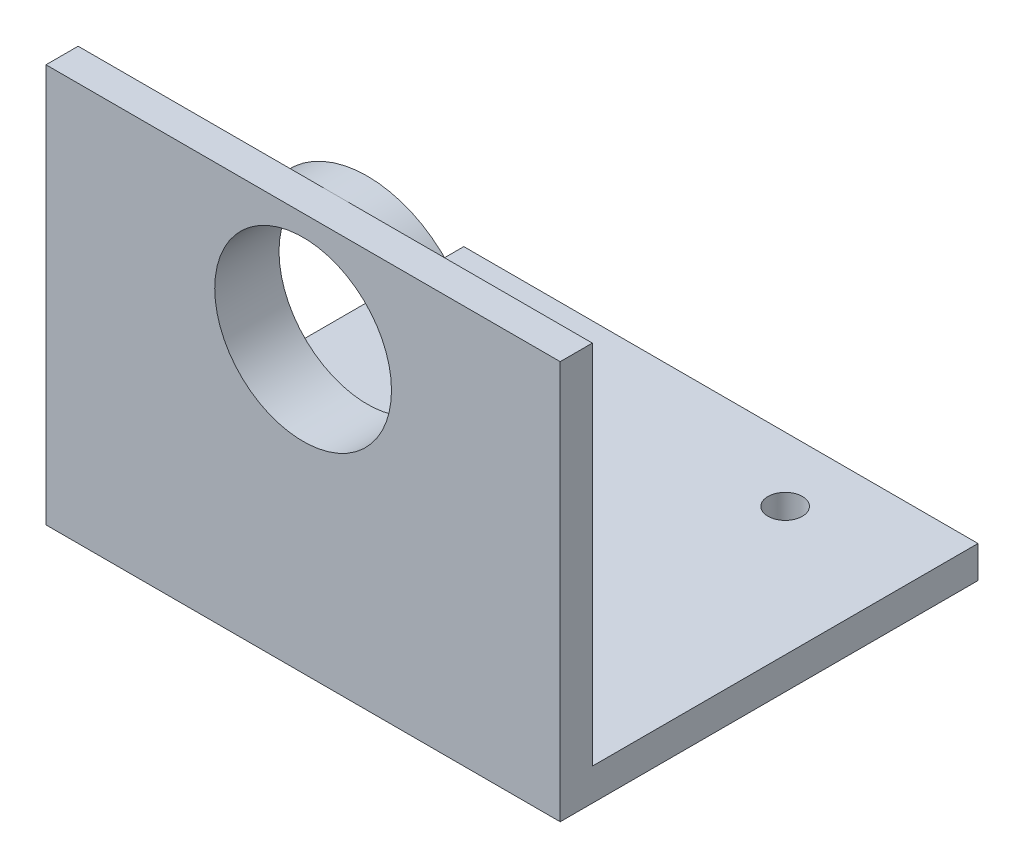
SolidWorks part; units mm, degrees
material "6061 Alloy"
ref_plane "Front Plane" through (0, 0, 0) normal (0, 0, 1) x (1, 0, 0)
ref_plane "Top Plane" through (0, 0, 0) normal (0, 1, 0) x (1, 0, 0)
ref_plane "Right Plane" through (0, 0, 0) normal (1, 0, 0) x (0, 0, -1)
sketch "Sketch2" plane through (0, 0, 0) normal (0, 1, 0) x (1, 0, 0)
  line L1 (-25.4, -12.7) -> (25.4, -12.7)
  line L2 (-25.4, -12.7) -> (-25.4, 12.7)
  line L4 (25.4, -12.7) -> (25.4, 12.7)
  line L5 (-25.4, -12.7) -> (25.4, 12.7) construction
  line L6 (-25.4, 12.7) -> (25.4, -12.7) construction
  line L8 (-25.4, 12.7) -> (-25.4, 25.4)
  line L9 (-25.4, 25.4) -> (25.4, 25.4)
  line L10 (25.4, 12.7) -> (25.4, 25.4)
  line L11 (0, 0) -> (0, 25.4) construction
  line L12 (-12.7, 19.05) -> (12.7, 19.05) construction
  point P0 (0, 0)
  point P6 (0, 19.05)
  point P14 (-12.7, 19.05)
  point P15 (12.7, 19.05)
  dimension "D1" = 50.8
  dimension "D2" = 25.4
  dimension "D3" = 12.7
  dimension "D4" = 25.4
  dimension "D5" = 6.35
extrude "Boss-Extrude1" add sketch "Sketch2" along normal blind 3.175
sketch "Sketch3" plane through (0, 3.175, 0) normal (0, 1, 0) x (1, 0, 0)
  line L0 (-25.4, -12.7) -> (25.4, -12.7) construction
  line L1 (-22.225, -9.525) -> (22.225, -9.525)
  line L2 (-22.225, -9.525) -> (-22.225, 9.525)
  line L3 (-22.225, 9.525) -> (22.225, 9.525)
  line L4 (22.225, -9.525) -> (22.225, 9.525)
  line L5 (-22.225, -9.525) -> (22.225, 9.525) construction
  line L6 (-22.225, 9.525) -> (22.225, -9.525) construction
  line L7 (-25.4, 25.4) -> (-25.4, -12.7) construction
  point P0 (0, 0)
  dimension "D2" = 3.175
  dimension "D1" = 3.175
extrude "Boss-Extrude2" [suppressed] add sketch "Sketch3" along normal blind 3.175
hole_wizard "M3 Clearance Hole1" positions "3DSketch1" profile "Sketch6" hole size "M3" standard "ANSI Metric" end condition through all
sketch3d "3DSketch1"
  point P0 (-12.7, 0, -19.05)
  point P3 (12.7, 0, -19.05)
sketch "Sketch6" plane through (-12.7, 0, -19.05) normal (1, 0, 0) x (0, 0, -1)
  line L0 (0, 0) -> (0, 3.175)
  line L1 (0, 3.175) -> (1.7, 3.175)
  line L2 (1.7, 3.175) -> (1.7, 0)
  line L5 (1.7, 0) -> (0, 0)
  line L11 (0, -6.35) -> (0, 107.95) construction
  dimension "Thru Hole Dia." = 3.4
  dimension "Thru Hole Depth" = 3.175
sketch "Sketch7" plane through (0, 0, 0) normal (0, -1, 0) x (1, 0, 0)
  line L0 (25.4, 12.7) -> (25.4, -25.4) construction
  line L1 (-25.4, 12.7) -> (25.4, 12.7)
  line L2 (-25.4, 12.7) -> (-25.4, 15.875)
  line L3 (-25.4, 15.875) -> (25.4, 15.875)
  line L4 (25.4, 12.7) -> (25.4, 15.875)
  dimension "D1" = 3.175
extrude "Boss-Extrude3" add sketch "Sketch7" against normal blind 39.37
sketch "Sketch8" plane through (0, 0, 12.7) normal (0, 0, -1) x (-1, 0, 0)
  line L0 (-10.795, 28.575) -> (-10.795, 3.175)
  line L2 (-10.795, 3.175) -> (10.795, 3.175)
  line L4 (10.795, 3.175) -> (10.795, 28.575)
  line L5 (25.4, 3.175) -> (-25.4, 3.175) construction
  arc A0 (10.795, 28.575) -> (-10.795, 28.575) centre (0, 28.575) ccw
  point P1 (0, 0)
  dimension "D2" = 21.59
  dimension "D1" = 25.4
extrude "Boss-Extrude4" add sketch "Sketch8" along normal blind 3.175
sketch "Sketch9" plane through (0, 0, 9.525) normal (0, 0, -1) x (-1, 0, 0)
  circle A0 centre (0, 28.575) radius 8.7312
  dimension "D1" = 17.4625
extrude "Cut-Extrude1" cut sketch "Sketch9" against normal through all
fillet "Fillet1" radius 3.175 2 edges at (-10.795, 3.175, 11.1125) (10.795, 3.175, 11.1125)
equation "\"D2@Sketch3\"=\"D1@Sketch3\""
